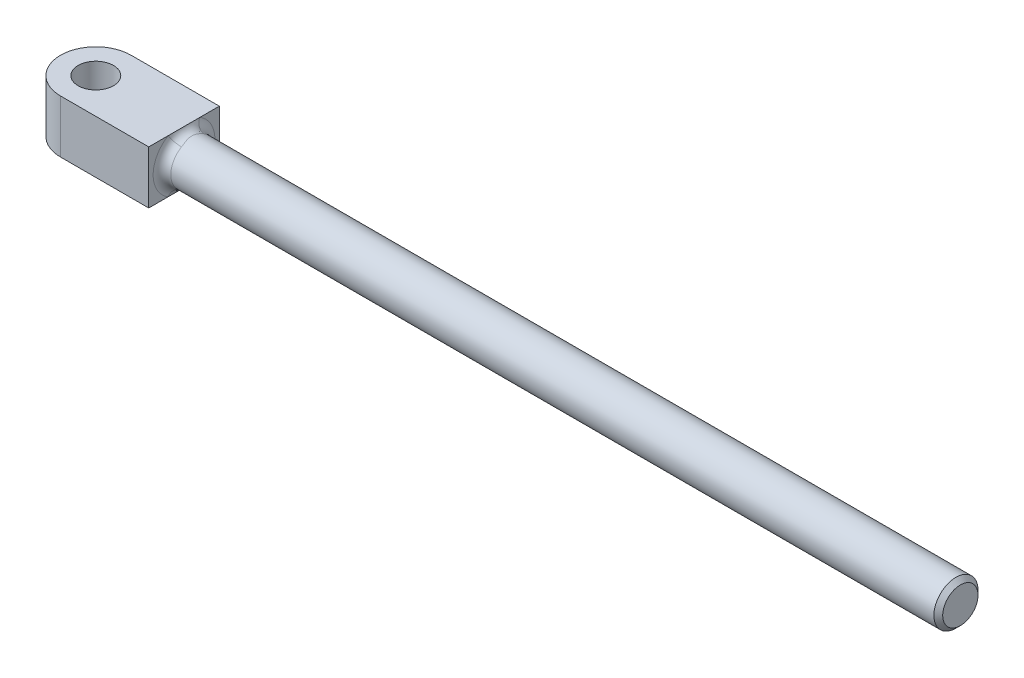
SolidWorks part; units mm, degrees
ref_plane "Front Plane" through (0, 0, 0) normal (0, 0, 1) x (1, 0, 0)
ref_plane "Top Plane" through (0, 0, 0) normal (0, 1, 0) x (1, 0, 0)
ref_plane "Right Plane" through (0, 0, 0) normal (1, 0, 0) x (0, 0, -1)
sketch "Sketch1" plane through (0, 0, 0) normal (1, 0, 0) x (0, 0, -1)
  circle A0 centre (0, 0) radius 2.5
  dimension "D1" = 5
extrude "Boss-Extrude1" add sketch "Sketch1" along normal mid plane 88
cosmetic thread "Cosmetic Thread1" parameters "D1"=14, "D2"=4.11
sketch "Sketch2" plane through (0, 0, 0) normal (0, 1, 0) x (1, 0, 0)
  line L0 (0, 0) -> (-49, 0) construction
  line L2 (-44, -4) -> (-54, -4)
  line L3 (-44, -4) -> (-44, 4)
  line L4 (-44, 4) -> (-54, 4)
  line L6 (-44, -4) -> (-54, 4) construction
  line L7 (-44, 4) -> (-54, -4) construction
  arc A0 (-54, 4) -> (-54, -4) centre (-54, 0) ccw
  circle A1 centre (-54, 0) radius 2
  dimension "D4" = 4
  dimension "D1" = 49
  dimension "D2" = 10
  dimension "D3" = 8
extrude "Boss-Extrude2" add sketch "Sketch2" along normal mid plane 6
fillet "Fillet1" radius 1 1 edges at (-44, 0, 2.5)
chamfer "Chamfer1" distance 0.5 angle 45 1 edges at (44, 0, -2.5)
